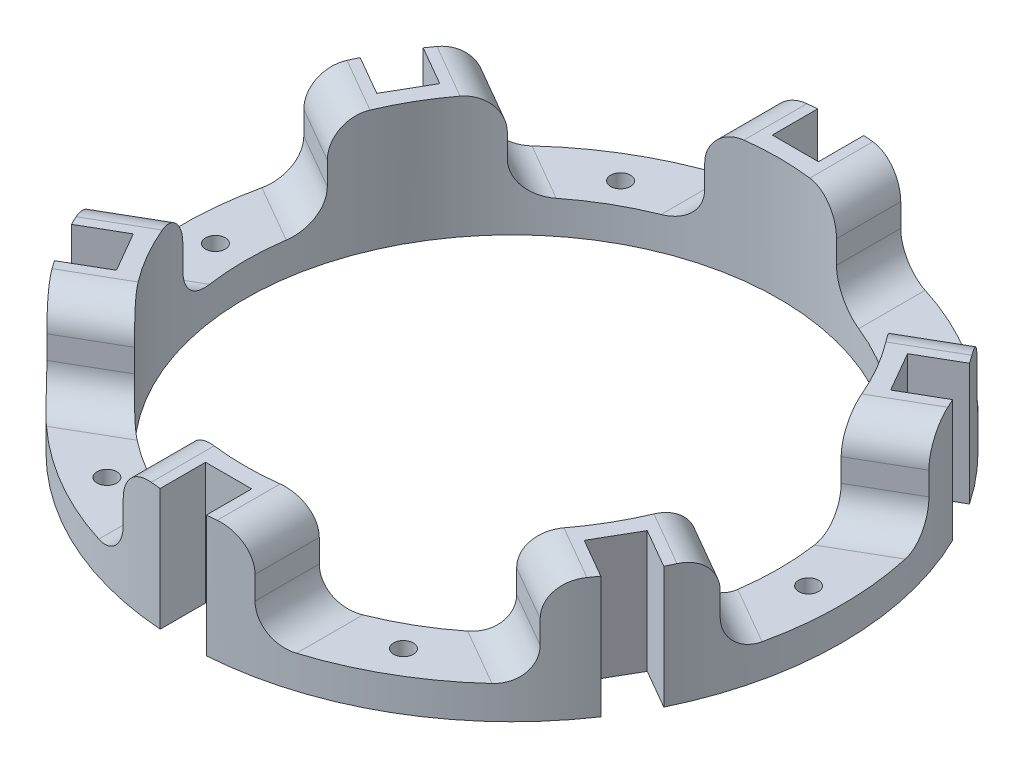
SolidWorks part; units mm, degrees
ref_plane "Спереди" through (0, 0, 0) normal (0, 0, 1) x (1, 0, 0)
ref_plane "Сверху" through (0, 0, 0) normal (0, 1, 0) x (1, 0, 0)
ref_plane "Справа" through (0, 0, 0) normal (1, 0, 0) x (0, 0, -1)
sketch "Эскиз1" plane through (0, 0, 0) normal (0, 1, 0) x (1, 0, 0)
  circle A0 centre (0, 0) radius 81
  circle A1 centre (0, 0) radius 100
  dimension "D1" = 200
  dimension "D2" = 162
extrude "Бобышка-Вытянуть1" add sketch "Эскиз1" along normal blind 10
sketch "Эскиз2" plane through (0, 10, 0) normal (0, 1, 0) x (1, 0, 0)
  line L0 (0, 0) -> (0, 93) construction
  line L1 (-7, 100) -> (7, 100)
  line L2 (-7, 100) -> (-7, 86)
  line L3 (-7, 86) -> (7, 86)
  line L4 (7, 100) -> (7, 86)
  line L5 (-7, 100) -> (7, 86) construction
  line L6 (-7, 86) -> (7, 100) construction
  circle A0 centre (0, 0) radius 100 construction
  point P0 (0, 93)
  dimension "D1" = 14
  dimension "D2" = 14
ref_plane "Плоскость1" through (0, 0, -100) normal (0, 0, -1) x (-1, 0, 0)
sketch "Эскиз5" plane through (0, 10, 0) normal (0, 1, 0) x (1, 0, 0)
  line L0 (-20, 78.492) -> (-20, 97.9796)
  line L1 (20, 78.492) -> (20, 97.9796)
  line L3 (0, 93) -> (-20, 93) construction
  line L4 (-7, 100) -> (7, 86) construction
  line L5 (0, 93) -> (20, 93) construction
  arc A0 (-20, 78.492) -> (20, 78.492) centre (0, 0) cw
  circle A1 centre (0, 0) radius 81 construction
  arc A2 (-20, 97.9796) -> (20, 97.9796) centre (0, 0) cw
  circle A3 centre (0, 0) radius 100 construction
  dimension "D1" = 40
extrude "Бобышка-Вытянуть2" add sketch "Эскиз5" along normal blind 27
extrude "Вырез-Вытянуть2" cut sketch "Эскиз2" along normal through all and the other way through all contours L3 L4 L1 L2
fillet "Скругление1" radius 10 4 edges at (-20, 10, -88.2358) (-20, 37, -88.2358) (20, 10, -88.2358) (20, 37, -88.2358)
pattern_circular "Круговой массив2" count 6 over 360 about axis through (0, 10, 0) along (0, 1, 0) of "Скругление1", "Вырез-Вытянуть2", "Бобышка-Вытянуть2"
sketch "Эскиз6" plane through (0, 10, 0) normal (0, 1, 0) x (1, 0, 0)
  line L0 (0, 0) -> (-45, 77.9423) construction
  line L1 (0, 0) -> (0, 93) construction
  circle A0 centre (0, 0) radius 90 construction
  circle A1 centre (-45, 77.9423) radius 3
  dimension "D1" = 180
  dimension "D3" = 6
  dimension "D2" = 30
extrude "Вырез-Вытянуть3" cut sketch "Эскиз6" against normal through all
pattern_circular "Круговой массив3" count 6 over 360 about axis through (0, 10, 0) along (0, 1, 0) of "Вырез-Вытянуть3"
